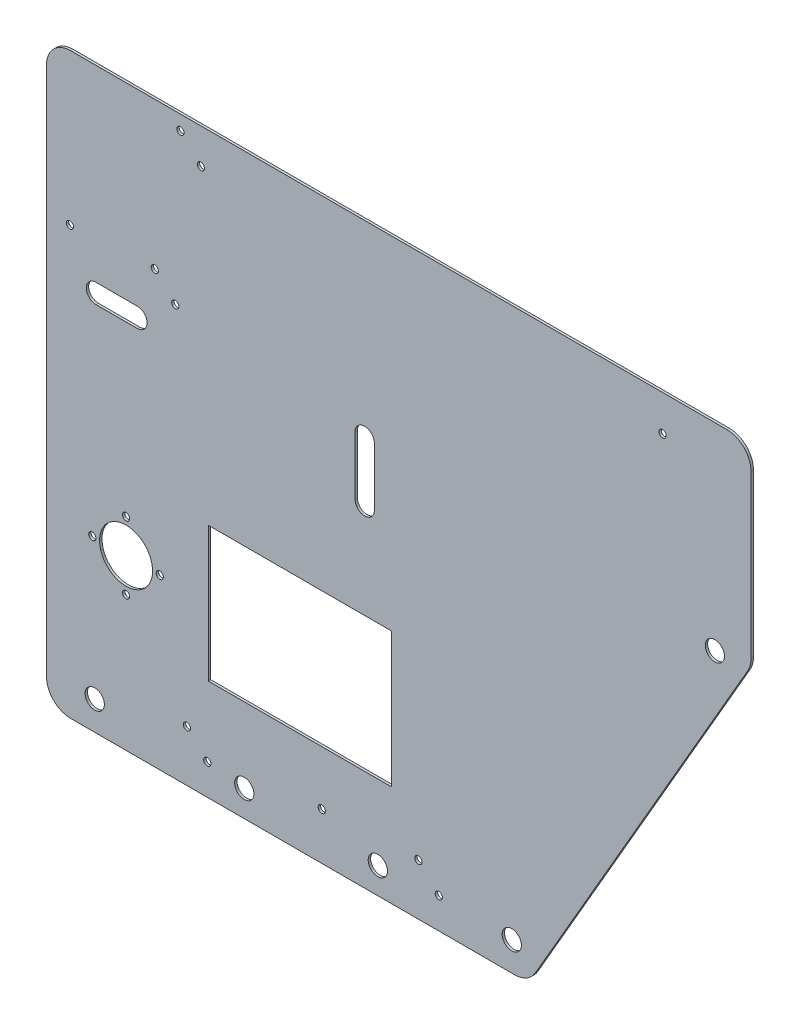
SolidWorks part; units mm, degrees
ref_plane "Front Plane" through (0, 0, 0) normal (0, 0, 1) x (1, 0, 0)
ref_plane "Top Plane" through (0, 0, 0) normal (0, 1, 0) x (1, 0, 0)
ref_plane "Right Plane" through (0, 0, 0) normal (1, 0, 0) x (0, 0, -1)
sketch "Sketch1" plane through (0, 0, 0) normal (0, 0, 1) x (1, 0, 0)
  line L0 (100, 80) -> (192.376, 80)
  line L1 (-100, -80) -> (100, -80)
  line L2 (-100, -80) -> (-100, 80)
  line L3 (-100, 80) -> (100, 80)
  line L4 (100, -80) -> (100, 80)
  line L5 (-100, -80) -> (100, 80) construction
  line L6 (-100, 80) -> (100, -80) construction
  line L7 (192.376, 80) -> (100, -80)
  line L8 (100, 80) -> (100, -80)
  line L10 (-100, 80) -> (192.376, 80)
  line L11 (-100, 80) -> (-100, 110)
  line L12 (-100, 110) -> (192.376, 110)
  line L13 (192.376, 80) -> (192.376, 110)
  point P0 (0, 0)
  dimension "D1" = 160
  dimension "D2" = 200
  dimension "D3" = 30
  dimension "D4" = 30
extrude "Boss-Extrude1" add sketch "Sketch1" along normal blind 1 contours L1 L4 L3 L2 | L7 L0 L4 | L11 L10 L13 L12 region at (0, 0, 0) region at (130.792, 26.6667, 0)
sketch "Sketch2" plane through (0, 0, 1) normal (0, 0, 1) x (1, 0, 0)
  line L0 (-100, -80) -> (100, -80) construction
  line L1 (192.376, 80) -> (100, -80) construction
  line L2 (-100, -80) -> (-100, 110) construction
  line L3 (-100, 110) -> (192.376, 110) construction
  line L4 (-79.5166, 78) -> (-62.3003, 78) construction
  line L7 (-100, -80) -> (-100, 110) construction
  line L8 (-29.8584, 15) -> (-29.8584, -35) construction
  line L9 (-79.5166, 82) -> (-62.3003, 82)
  line L10 (-79.5166, 74) -> (-62.3003, 74)
  line L11 (-32.8584, 18) -> (43.1416, 18)
  line L12 (-32.8584, 18) -> (-32.8584, -38)
  line L13 (-32.8584, -38) -> (43.1416, -38)
  line L14 (43.1416, 18) -> (43.1416, -38)
  line L15 (20.1416, 15) -> (-29.8584, 15) construction
  line L17 (40.1416, -35) -> (40.1416, 15) construction
  line L18 (32.0262, 82) -> (32.0262, 57.7776) construction
  line L19 (36.0262, 82) -> (36.0262, 57.7776)
  line L20 (28.0262, 82) -> (28.0262, 57.7776)
  circle A0 centre (93.0718, -68) radius 4
  circle A1 centre (177.3649, 78) radius 4
  circle A2 centre (-67, -10) radius 11
  circle A3 centre (-80, -68) radius 4
  circle A4 centre (-53, -10) radius 1.5
  circle A5 centre (-67, 4) radius 1.5
  circle A6 centre (-81, -10) radius 1.5
  circle A7 centre (-67, -24) radius 1.5
  circle A10 centre (32.0262, 70) radius 4 construction
  arc A11 (-79.5166, 82) -> (-79.5166, 74) centre (-79.5166, 78) ccw
  arc A12 (-62.3003, 74) -> (-62.3003, 82) centre (-62.3003, 78) ccw
  circle A32 centre (62.7961, -67.2426) radius 1.5
  circle A33 centre (54.3108, -58.7574) radius 1.5
  circle A34 centre (-33.2742, -67.2426) radius 1.5
  circle A35 centre (-41.7595, -58.7574) radius 1.5
  circle A36 centre (14.2259, -60.5) radius 1.5
  circle A37 centre (-46.589, 90.4743) radius 1.5
  circle A38 centre (-55.0743, 98.9596) radius 1.5
  circle A39 centre (-90.2956, 97.2169) radius 1.5
  circle A40 centre (155.6518, 145.1456) radius 1.5
  arc A41 (36.0262, 82) -> (28.0262, 82) centre (32.0262, 82) ccw
  arc A42 (28.0262, 57.7776) -> (36.0262, 57.7776) centre (32.0262, 57.7776) ccw
  circle A43 centre (-17.9479, -69.1174) radius 4
  circle A44 centre (37.4944, -69.1174) radius 4
  point P12 (-70.9085, 78)
  point P65 (32.0262, 69.8888)
  dimension "D3" = 8
  dimension "D4" = 8
  dimension "D9" = 22
  dimension "D10" = 8
  dimension "D12" = 3
  dimension "D13" = 3
  dimension "D14" = 3
  dimension "D15" = 3
  dimension "D16" = 14
  dimension "D20" = 4
  dimension "D22" = 8
  dimension "D23" = 3
  dimension "D24" = 20
  dimension "D25" = 3
  dimension "D1" = 12
  dimension "D2" = 12
  dimension "D5" = 32
  dimension "D6" = 12
  dimension "D7" = 33
  dimension "D8" = 70
  dimension "D11" = 12
  dimension "D17" = 14
  dimension "D18" = 14
  dimension "D19" = 14
  dimension "D21" = 40
  dimension "D26" = 3
  dimension "D27" = 3
  dimension "D28" = 8
  dimension "D29" = 3
extrude "Cut-Extrude1" cut sketch "Sketch2" against normal blind 3
sketch "Sketch3" plane through (0, 0, 1) normal (0, 0, 1) x (1, 0, 0)
  line L0 (192.376, 80) -> (192.376, 110) construction
  line L1 (-100, 110) -> (192.376, 110)
  line L2 (-100, 110) -> (-100, 160)
  line L3 (-100, 160) -> (192.376, 160)
  line L4 (192.376, 110) -> (192.376, 160)
  dimension "D1" = 50
extrude "Boss-Extrude2" add sketch "Sketch3" against normal blind 1
fillet "Fillet1" radius 10 5 edges at (100, -80, 0.5) (-100, -80, 0.5) (-100, 160, 0.5) (192.376, 160, 0.5) (192.376, 80, 0.5)
sketch "Sketch4" plane through (0, 0, 1) normal (0, 0, 1) x (1, 0, 0)
  circle A2 centre (-44.4423, 153.9596) radius 1.5
  circle A3 centre (-35.957, 145.4743) radius 1.5
  circle A4 centre (155.6518, 145.1456) radius 1.5
  dimension "D1" = 3
extrude "Cut-Extrude2" cut sketch "Sketch4" against normal blind 11
